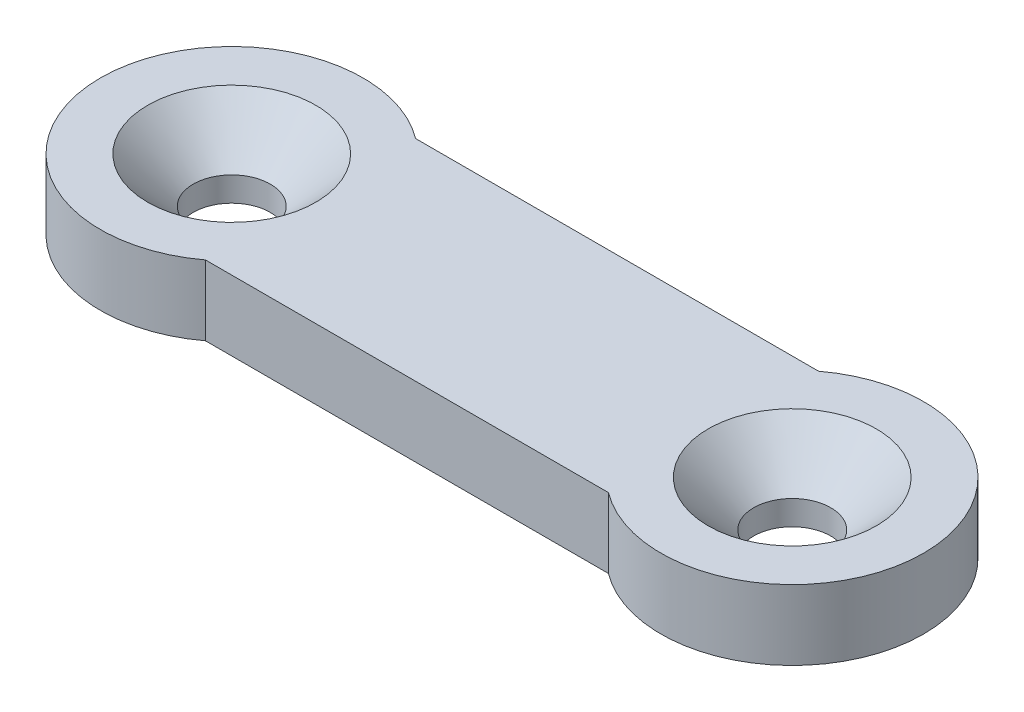
SolidWorks part; units mm, degrees
ref_plane "Front Plane" through (0, 0, 0) normal (0, 0, 1) x (1, 0, 0)
ref_plane "Top Plane" through (0, 0, 0) normal (0, 1, 0) x (1, 0, 0)
ref_plane "Right Plane" through (0, 0, 0) normal (1, 0, 0) x (0, 0, -1)
sketch "Sketch1" plane through (0, 0, 0) normal (0, 1, 0) x (1, 0, 0)
  line L0 (-8, 0) -> (8, 0) construction
  line L1 (-8, 3) -> (8, 3)
  line L2 (-8, -3) -> (8, -3)
  arc A0 (-8, 3) -> (-8, -3) centre (-8, 0) ccw
  arc A1 (8, -3) -> (8, 3) centre (8, 0) ccw
  circle A2 centre (-8, 0) radius 1.1
  circle A5 centre (8, 0) radius 1.1
  point P2 (0, 0)
  dimension "D1" = 2.2
  dimension "D2" = 16
  dimension "D3" = 6
extrude "Boss-Extrude1" add sketch "Sketch1" along normal blind 2
sketch "Sketch3" plane through (0, 2, 0) normal (0, 1, 0) x (1, 0, 0)
  circle A0 centre (-8, 0) radius 3.75
  circle A1 centre (8, 0) radius 3.75
  circle A2 centre (-8, 0) radius 1.1
  circle A3 centre (8, 0) radius 1.1
  circle A4 centre (-8, 0) radius 1.1 construction
  circle A5 centre (8, 0) radius 1.1 construction
  dimension "D1" = 7.5
extrude "Boss-Extrude3" add sketch "Sketch3" against normal up to surface (2 mm away) up to face at (0, 0, 0)
chamfer "Chamfer1" distance 1.3 angle 45 2 edges at (8, 2, 1.1) (-8, 2, 1.1)
